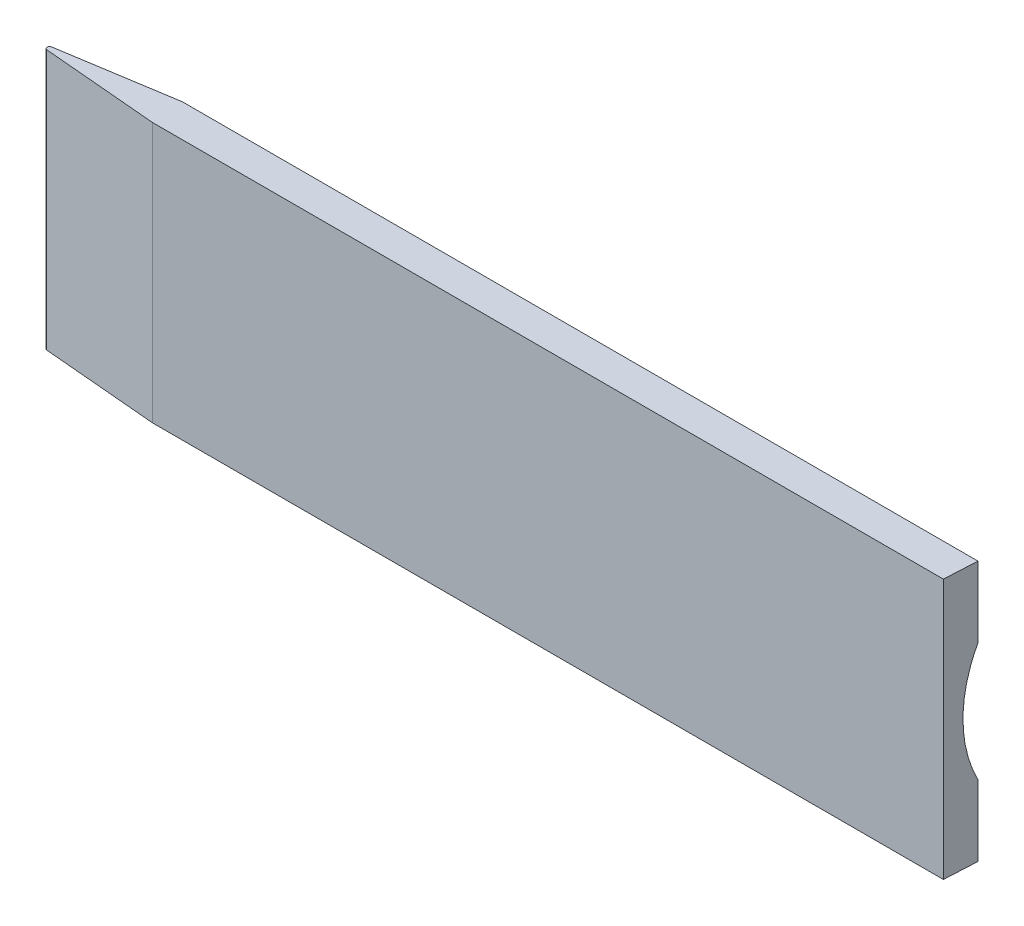
SolidWorks part; units mm, degrees
material "Acrylic (Medium-high impact)"
ref_plane "Front Plane" through (0, 0, 0) normal (0, 0, 1) x (1, 0, 0)
ref_plane "Top Plane" through (0, 0, 0) normal (0, 1, 0) x (1, 0, 0)
ref_plane "Right Plane" through (0, 0, 0) normal (1, 0, 0) x (0, 0, -1)
sketch "Sketch1" plane through (0, 0, 0) normal (0, 1, 0) x (1, 0, 0)
  line L0 (180, 5) -> (179.4699, -5.1156)
  line L1 (-63.7673, -5.1156) -> (179.4699, -5.1156)
  line L2 (-100, -1.3501) -> (-100, -1.1547)
  line L3 (-64.6456, 5) -> (180, 5)
  line L5 (-20.1726, -0.5604) -> (180, 5) construction
  line L6 (-20.1728, 0.5586) -> (180.349, -4.9939) construction
  line L7 (-99.4517, -0.5127) -> (-64.6456, 5)
  line L8 (-99.4067, -1.9976) -> (-63.7673, -5.1156)
  arc A0 (-99.4067, -1.9976) -> (-100, -1.3501) centre (-99.35, -1.3501) cw
  arc A1 (-99.4517, -0.5127) -> (-100, -1.1547) centre (-99.35, -1.1547) ccw
  point P0 (0, 0)
  point P15 (0, 0)
  point P16 (0, 0)
  point P19 (-100.1131, -1.1252)
  dimension "D6" = 0.65
  dimension "D1" = 10
  dimension "D2" = 280
  dimension "D3" = 87
  dimension "D4" = 99
  dimension "D5" = 95
extrude "Boss-Extrude1" add sketch "Sketch1" along normal blind 80
ref_plane "Plane1" through (180, 0, 0) normal (-1, 0, 0) x (0, 0, 1)
sketch "Sketch2" plane through (-100, 0, 0) normal (-1, 0, 0) x (0, 0, 1)
  line L0 (1.1547, 80) -> (1.1547, 0) construction
  circle A0 centre (-21.3453, 40) radius 22.5
  dimension "D1" = 45
sketch "Sketch3" plane through (180, 0, 8.6965) normal (1, 0, 0) x (0, 0, -1)
  circle A0 centre (49.3052, 40) radius 40
  dimension "D1" = 80
sketch3d "3DSketch1"
  line L0 (-100, 51.6621, -40.587) -> (102.382, 51.6621, -40.587)
  circle A0 centre (-100, 40, -21.3453) radius 22.5 construction
  point P6 (-122.5, 40, -21.3453)
loft "Cut-Loft2" cut profiles "Sketch2", "Sketch3" connector at (-100, 46.3723, -42.9241) connector at (180, 28.5511, -78.9352)
